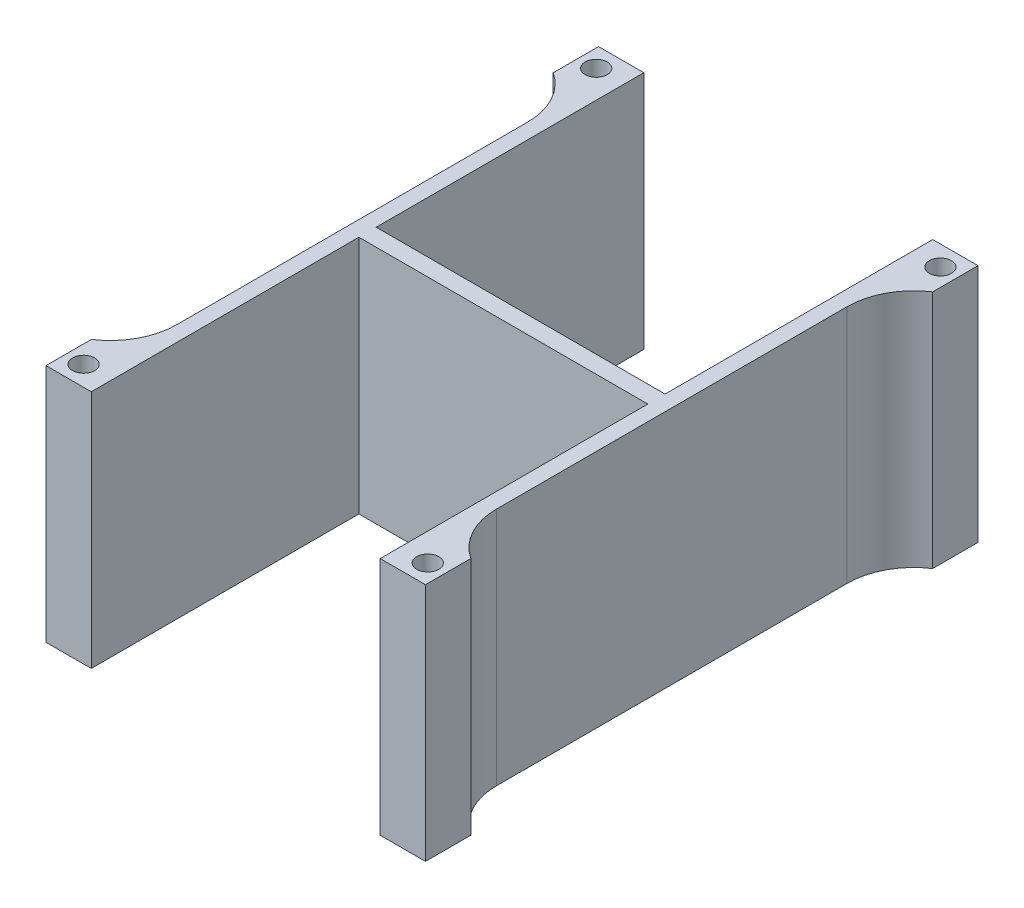
SolidWorks part; units mm, degrees
material "Alliage 1060"
ref_plane "Plan de dessus" through (0, 0, 0) normal (0, 0, 1) x (1, 0, 0)
ref_plane "Plan de droite" through (0, 0, 0) normal (0, 1, 0) x (1, 0, 0)
ref_plane "Plan de face" through (0, 0, 0) normal (1, 0, 0) x (0, 0, -1)
sketch "Esquisse1" plane through (0, 0, 0) normal (0, 0, 1) x (1, 0, 0)
  line L0 (43, 43) -> (0, 0) construction
  line L1 (0, 0) -> (43, 0)
  line L2 (0, 0) -> (0, 43)
  line L3 (0, 43) -> (43, 43)
  line L4 (43, 0) -> (43, 43)
  line L9 (45.5, -2.5) -> (21.5, 21.5) construction
  line L21 (-2.5, 43) -> (-2.5, -2.5)
  line L22 (-2.5, 43) -> (-2.5, 45.5)
  line L23 (-2.5, 45.5) -> (45.5, 45.5)
  line L25 (45.5, 43) -> (45.5, 45.5)
  line L26 (45.5, 43) -> (45.5, -2.5)
  line L28 (0, -2.5) -> (45.5, -2.5)
  line L29 (0, -2.5) -> (-2.5, -2.5)
  point P5 (-2.5, 43)
  dimension "D1" = 43
  dimension "D2" = 43
extrude "Boss.-Extru.1" add sketch "Esquisse1" along normal blind 40
sketch "Esquisse2" plane through (0, 0, 0) normal (0, 0, 1) x (1, 0, 0)
  line L5 (-2.5, 45.5) -> (45.5, 45.5)
  line L6 (-2.5, 45.5) -> (-2.5, -2.5)
  line L7 (-2.5, -2.5) -> (45.5, -2.5)
  line L8 (45.5, 45.5) -> (45.5, -2.5)
extrude "Boss.-Extru.2" add sketch "Esquisse2" against normal blind 1.5
sketch "Esquisse5" plane through (0, 45.5, 0) normal (0, 1, 0) x (1, 0, 0)
  line L0 (17.5, -3.8) -> (25.5, -3.8)
  line L1 (25.5, -8.8) -> (17.5, -8.8)
  line L2 (25.5, -3.8) -> (25.5, -8.8)
  line L3 (17.5, -3.8) -> (17.5, -8.8)
  line L4 (45.5, -40) -> (45.5, 1.5) construction
  line L5 (-2.5, -19.25) -> (45.5, -19.25) construction
  line L6 (-2.5, -40) -> (-2.5, 1.5) construction
  line L7 (21.5, 1.5) -> (21.5, -40) construction
  line L8 (45.5, 1.5) -> (-2.5, 1.5) construction
  line L9 (45.5, -40) -> (-2.5, -40) construction
  point P5 (21.5, -8.8)
  point P17 (21.5, -3.8)
  dimension "D1" = 4
  dimension "D2" = 5.3
extrude "Enlèv. mat.-Extru.3" cut sketch "Esquisse5" against normal up to next
sketch "Esquisse6" plane through (0, 0, 40) normal (0, 0, 1) x (1, 0, 0)
  line L1 (-4.2276, 0) -> (50.5536, 0)
  line L2 (-4.2276, 0) -> (-4.2276, -3.0788)
  line L3 (-4.2276, -3.0788) -> (50.5536, -3.0788)
  line L4 (50.5536, 0) -> (50.5536, -3.0788)
extrude "Enlèv. mat.-Extru.4" cut sketch "Esquisse6" against normal up to next
mirror "Symétrie1" about plane through (0, 0, -1.5) normal (0, 0, 1) of bodies 113
sketch "Esquisse7" plane through (0, 45.5, 0) normal (0, 1, 0) x (1, 0, 0)
  line L0 (-2.5, 7.8) -> (0, 7.8)
  line L1 (-2.5, 43) -> (45.5, 43)
  line L2 (-2.5, 43) -> (-2.5, 30.4)
  line L3 (-2.5, -40) -> (45.5, -40)
  line L4 (45.5, 43) -> (45.5, 30.4)
  line L13 (-2.5, 30.4) -> (0, 30.4)
  line L15 (-2.5, 25.4) -> (0, 25.4)
  line L16 (0, 30.4) -> (0, 25.4)
  line L17 (0, 12.8) -> (0, 7.8)
  line L18 (-2.5, 12.8) -> (0, 12.8)
  line L19 (-2.5, -9.8) -> (0, -9.8)
  line L20 (0, -4.8) -> (0, -9.8)
  line L21 (-2.5, -4.8) -> (0, -4.8)
  line L22 (-2.5, -27.4) -> (0, -27.4)
  line L23 (0, -22.4) -> (0, -27.4)
  line L24 (-2.5, -22.4) -> (0, -22.4)
  line L25 (-2.5, 25.4) -> (-2.5, 12.8)
  line L26 (45.5, 30.4) -> (43, 30.4)
  line L27 (43, 30.4) -> (43, 25.4)
  line L28 (45.5, 25.4) -> (43, 25.4)
  line L29 (45.5, 12.8) -> (43, 12.8)
  line L30 (43, 12.8) -> (43, 7.8)
  line L31 (45.5, 7.8) -> (43, 7.8)
  line L32 (45.5, -27.4) -> (43, -27.4)
  line L33 (43, -22.4) -> (43, -27.4)
  line L34 (45.5, -22.4) -> (43, -22.4)
  line L35 (45.5, -4.8) -> (43, -4.8)
  line L36 (45.5, -9.8) -> (43, -9.8)
  line L37 (43, -4.8) -> (43, -9.8)
  line L38 (-2.5, 7.8) -> (-2.5, -4.8)
  line L39 (-2.5, -9.8) -> (-2.5, -22.4)
  line L40 (-2.5, -27.4) -> (-2.5, -40)
  line L41 (45.5, -27.4) -> (45.5, -40)
  line L42 (45.5, -9.8) -> (45.5, -22.4)
  line L43 (45.5, 7.8) -> (45.5, -4.8)
  line L44 (45.5, 25.4) -> (45.5, 12.8)
  dimension "D1" = 5
  dimension "D2" = 12.6
  dimension "D3" = 4
extrude "Enlèv. mat.-Extru.5" cut sketch "Esquisse7" against normal blind 9.5
sketch "Esquisse8" plane through (0, 36, 0) normal (0, 1, 0) x (1, 0, 0)
  line L0 (-0.2, 43) -> (-0.2, 2.8)
  line L1 (0, 43) -> (-2.5, 43) construction
  line L2 (-0.2, 2.8) -> (43.2, 2.8)
  line L3 (43.2, 2.8) -> (43.2, 43)
  line L4 (45.5, 43) -> (43, 43) construction
  line L5 (43.2, 43) -> (43, 43)
  line L6 (43, 43) -> (43, 3)
  line L7 (43, 3) -> (0, 3)
  line L8 (0, 3) -> (0, 43)
  line L9 (0, 43) -> (-0.2, 43)
  line L10 (-2.5, 1.5) -> (45.5, 1.5) construction
  line L11 (-2.5, 7.8) -> (-2.5, -4.8) construction
  line L12 (45.5, -4.8) -> (45.5, 7.8) construction
  line L13 (0, 0) -> (0, -40)
  line L14 (43, 0) -> (0, 0)
  line L15 (43, -40) -> (43, 0)
  line L16 (43.2, -40) -> (43, -40)
  line L17 (43.2, 0.2) -> (43.2, -40)
  line L18 (-0.2, 0.2) -> (43.2, 0.2)
  line L19 (-0.2, -40) -> (-0.2, 0.2)
  line L20 (0, -40) -> (-0.2, -40)
  dimension "D1" = 0.2
  dimension "D2" = 0.2
  dimension "D3" = 0.2
extrude "Enlèv. mat.-Extru.6" cut sketch "Esquisse8" against normal through all and the other way through all
sketch "Esquisse9" plane through (0, 45.5, 0) normal (0, 1, 0) x (1, 0, 0)
  line L1 (-19.7791, 47.0897) -> (62.4768, 47.0897)
  line L2 (-19.7791, 47.0897) -> (-19.7791, -43.8609)
  line L3 (-19.7791, -43.8609) -> (62.4768, -43.8609)
  line L4 (62.4768, 47.0897) -> (62.4768, -43.8609)
extrude "Enlèv. mat.-Extru.7" cut sketch "Esquisse9" against normal up to surface (9.5 mm away) up to face at (-1.35, 36, 33.7)
sketch "Esquisse10" plane through (45.5, 0, 0) normal (1, 0, 0) x (0, 0, -1)
  line L0 (-40, 36) -> (-34, 36)
  line L1 (-40, 36) -> (43, 36) construction
  line L2 (-34, 36) -> (-34, 0)
  line L3 (-34, 0) -> (-40, 0)
  line L4 (-40, 0) -> (-40, 36) construction
  line L5 (-40, 0) -> (-40, 36)
  line L6 (43, 0) -> (-40, 0) construction
  line L7 (1.5, 36) -> (1.5, -2.9956) construction
  line L8 (43, 0) -> (43, 36)
  line L9 (37, 0) -> (43, 0)
  line L10 (37, 36) -> (37, 0)
  line L11 (43, 36) -> (37, 36)
  dimension "D1" = 6
  dimension "D2" = 0
extrude "Boss.-Extru.3" add sketch "Esquisse10" along normal blind 6
fillet "Congé1" radius 10 2 edges at (45.5, 18, 34) (45.5, 18, -37)
sketch "Esquisse11" plane through (-2.5, 0, 0) normal (-1, 0, 0) x (0, 0, 1)
  line L0 (40, 0) -> (-43, 0) construction
  line L1 (-43, 36) -> (-37, 36)
  line L2 (-43, 36) -> (-43, 0)
  line L3 (-43, 0) -> (-37, 0)
  line L4 (-37, 36) -> (-37, 0)
  line L5 (-1.5, 36) -> (-1.5, 0.0985) construction
  line L6 (-43, 36) -> (40, 36) construction
  line L7 (40, 0) -> (34, 0)
  line L8 (34, 36) -> (34, 0)
  line L9 (40, 36) -> (34, 36)
  line L10 (40, 36) -> (40, 0)
  dimension "D1" = 6
extrude "Boss.-Extru.4" add sketch "Esquisse11" along normal blind 6
fillet "Congé2" radius 10 2 edges at (-2.5, 18, 34) (-2.5, 18, -37)
sketch "Esquisse12" plane through (0, 36, 0) normal (0, 1, 0) x (1, 0, 0)
  line L0 (-8.5, 37) -> (-0.2, 37) construction
  line L1 (-0.2, 43) -> (-0.2, 2.8) construction
  line L2 (21.5, 2.8) -> (21.5, 53.694) construction
  line L3 (-0.2, 43) -> (-8.5, 43) construction
  line L4 (-4.35, 37) -> (-4.35, 43) construction
  line L5 (-0.2, 2.8) -> (43.2, 2.8) construction
  line L6 (-2.5, 1.5) -> (52.7549, 1.5) construction
  line L7 (-2.5, 27.8348) -> (-2.5, -24.8348) construction
  circle A0 centre (-4.35, 40) radius 1.66
  circle A1 centre (47.35, 40) radius 1.66
  circle A2 centre (47.35, -37) radius 1.66
  circle A3 centre (-4.35, -37) radius 1.66
  dimension "D1" = 3.32
extrude "Enlèv. mat.-Extru.8" cut sketch "Esquisse12" against normal blind 10
sketch "Esquisse13" plane through (0, 36, 0) normal (0, 1, 0) x (1, 0, 0)
  line L0 (51.5, 43) -> (51.5, 37) construction
  line L10 (51.5, -34) -> (51.5, -40) construction
  line L12 (55.6579, 45.9368) -> (55.6579, 30.8106)
  line L13 (55.6579, -42.9368) -> (55.6579, -27.8106)
  line L14 (55.6579, -42.9368) -> (50, -42.9368)
  line L15 (50, -42.9368) -> (50, -27.8106)
  line L16 (55.6579, -27.8106) -> (50, -27.8106)
  line L17 (55.6579, 30.8106) -> (50, 30.8106)
  line L18 (50, 45.9368) -> (50, 30.8106)
  line L19 (55.6579, 45.9368) -> (50, 45.9368)
  line L20 (21.5, 2.8) -> (21.5, 48.8459) construction
  line L21 (-0.2, 2.8) -> (43.2, 2.8) construction
  line L22 (-12.6579, 45.9368) -> (-7, 45.9368)
  line L23 (-7, 45.9368) -> (-7, 30.8106)
  line L24 (-12.6579, 30.8106) -> (-7, 30.8106)
  line L25 (-12.6579, -27.8106) -> (-7, -27.8106)
  line L26 (-7, -42.9368) -> (-7, -27.8106)
  line L27 (-12.6579, -42.9368) -> (-7, -42.9368)
  line L28 (-12.6579, -42.9368) -> (-12.6579, -27.8106)
  line L29 (-12.6579, 45.9368) -> (-12.6579, 30.8106)
  dimension "D1" = 1.5
  dimension "D2" = 1.5
extrude "Enlèv. mat.-Extru.9" cut sketch "Esquisse13" against normal through all
